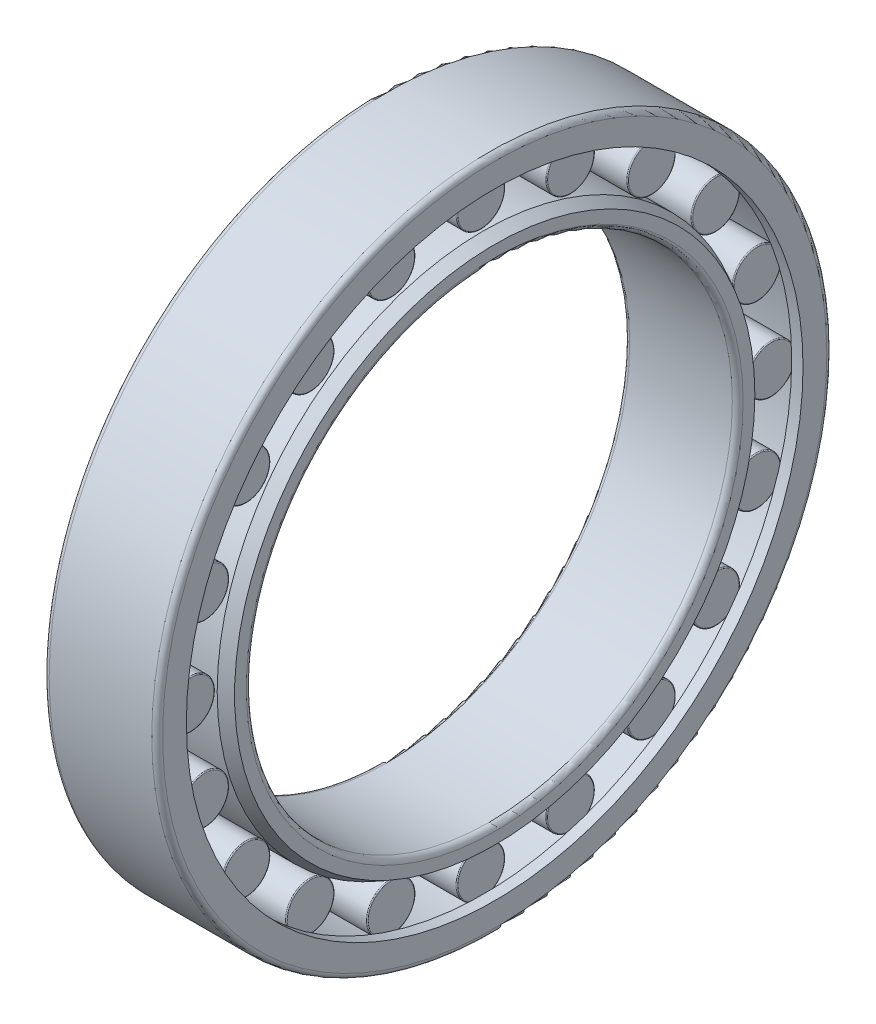
SolidWorks part; units mm, degrees
ref_plane "Plane1" through (0, 0, 0) normal (0, 0, 1) x (1, 0, 0)
ref_plane "Plane2" through (0, 0, 0) normal (0, 1, 0) x (1, 0, 0)
ref_plane "Plane3" through (0, 0, 0) normal (1, 0, 0) x (0, 0, -1)
sketch "Clipboard" plane through (0, 0, 0) normal (0, 0, 1) x (1, 0, 0)
  line L0 (-10, 0) -> (10, 0) construction
  line L1 (0, 0) -> (185.2698, -67.4327)
  line L2 (0, 0) -> (101.017, 36.7672)
  line L3 (0, 0) -> (218.798, -79.636)
  line L4 (0, 0) -> (-22.3471, -0.7804)
  dimension "Race_OD" = 232.84
  dimension "Race_ID" = 197.16
sketch "OutRacSke" plane through (0, 0, 0) normal (0, 0, 1) x (1, 0, 0)
  line L0 (-16.8, 114.1887) -> (-21, 114.1887)
  line L1 (-21, 114.1887) -> (-21, 123)
  line L2 (-19, 125) -> (19, 125)
  line L3 (21, 123) -> (21, 114.1888)
  line L4 (21, 114.1888) -> (16.8, 114.1888)
  line L5 (16.8, 114.1888) -> (16.8, 116.42)
  line L6 (16.8, 116.42) -> (-16.8, 116.42)
  line L7 (-16.8, 116.42) -> (-16.8, 114.1887)
  line L8 (-90, 0) -> (90, 0) construction
  arc A0 (-21, 123) -> (-19, 125) centre (-19, 123) cw
  arc A1 (19, 125) -> (21, 123) centre (19, 123) cw
  dimension "Race_OD" = 232.84
  dimension "radius" = 2
  dimension "halfWidth" = 21
  dimension "groove_dp" = 2.2313
  dimension "Cyl_Len" = 33.6
revolve "OuterRace" add sketch "OutRacSke" angle 360 about L8 reverse direction yes
sketch "RolDetSke" plane through (0, 0, 0) normal (0, 0, 1) x (1, 0, 0)
  line L0 (-15.96, 116.068) -> (-15.96, 107.5)
  line L1 (-15.96, 107.5) -> (15.96, 107.5)
  line L2 (15.96, 107.5) -> (15.96, 116.068)
  line L3 (15.603, 116.425) -> (-15.603, 116.425)
  line L4 (-33.6, 107.5) -> (33.6, 107.5) construction
  arc A0 (15.96, 116.068) -> (15.603, 116.425) centre (15.603, 116.068) ccw
  arc A1 (-15.603, 116.425) -> (-15.96, 116.068) centre (-15.603, 116.068) ccw
  dimension "radius" = 0.357
  dimension "Roller_diameter" = 17.85
  dimension "halfLength" = 15.96
revolve "RollerDetailed" add sketch "RolDetSke" angle 360 about L4 reverse direction yes
ref_axis "Axis1" through (-50, 0, 0) along (1, 0, 0)
sketch "RolSimSke" plane through (0, 101.6, 0) normal (0, 0, 1) x (1, 0, 0)
  line L0 (-15.96, 14.468) -> (-15.96, -2.668)
  line L1 (25.4, -101.6) -> (-25.4, -101.6) construction
  line L2 (15.96, -2.668) -> (15.96, 14.468)
  line L3 (15.603, 14.825) -> (-15.603, 14.825)
  line L5 (15.603, -3.025) -> (-15.603, -3.025)
  arc A0 (15.96, 14.468) -> (15.603, 14.825) centre (15.603, 14.468) ccw
  arc A1 (-15.603, 14.825) -> (-15.96, 14.468) centre (-15.603, 14.468) ccw
  arc A2 (15.96, -2.668) -> (15.603, -3.025) centre (15.603, -2.668) cw
  arc A3 (-15.603, -3.025) -> (-15.96, -2.668) centre (-15.603, -2.668) cw
  dimension "radius" = 0.357
  dimension "D1" = 98.575
  dimension "Roller_diameter" = 17.85
  dimension "halfLength" = 15.96
revolve "RollersSimplified" [suppressed] add sketch "RolSimSke" angle 360 about L1
sketch "InsRacSke" plane through (0, 0, 0) normal (0, 0, 1) x (1, 0, 0)
  line L0 (-16.8, 98.58) -> (-21, 96.3487)
  line L1 (-21, 96.3487) -> (-21, 92)
  line L2 (-19, 90) -> (19, 90)
  line L3 (21, 92) -> (21, 96.3487)
  line L4 (21, 96.3487) -> (16.8, 98.58)
  line L5 (16.8, 98.58) -> (-16.8, 98.58)
  line L6 (-90, 0) -> (90, 0) construction
  line L7 (0, 0) -> (0, 177.8) construction
  arc A0 (-21, 92) -> (-19, 90) centre (-19, 92) ccw
  arc A1 (19, 90) -> (21, 92) centre (19, 92) ccw
  dimension "radius" = 2
  dimension "Race_ID" = 197.16
  dimension "Width" = 42
  dimension "halfWidth" = 21
  dimension "groove_dp" = 2.2313
  dimension "Cyl_Len" = 33.6
revolve "InnerRace" add sketch "InsRacSke" angle 360 about L6 reverse direction yes
pattern_circular "RollersDetailed" count 20 every 18 about axis through (-50, 0, 0) along (1, 0, 0) of "RollerDetailed"
sketch "CagSpiSke" plane through (0, 0, 0) normal (0, 0, 1) x (1, 0, 0)
  line L0 (18.9, 105.2687) -> (18.9, 109.7313)
  line L1 (18.9, 109.7313) -> (-18.9, 109.7313)
  line L2 (-18.9, 109.7313) -> (-18.9, 105.2687)
  line L3 (-18.9, 105.2687) -> (18.9, 105.2687)
  line L4 (-90, 0) -> (90, 0) construction
revolve "CageSpine" [suppressed] add sketch "CagSpiSke" angle 360 about L4
equation "\"CLdia@Clipboard\" =  ( \"Race_OD@Clipboard\" + \"Race_ID@Clipboard\" )  / 4"
equation "\"Race_OD@OutRacSke\" = \"Race_OD@Clipboard\""
equation "\"halfCylLen@OutRacSke\" = \"Cyl_Len@OutRacSke\" / 2"
equation "\"RolCLRad@RolDetSke\" = \"CLdia@Clipboard\""
equation "\"Roller_diameter@RolDetSke\" =  ( \"Race_OD@Clipboard\" - \"Race_ID@Clipboard\" )  / 2 + .01"
equation "\"Roller_diameter@RolSimSke\" =  ( \"Race_OD@Clipboard\" - \"Race_ID@Clipboard\" )  / 2 + .01"
equation "\"radius@RolDetSke\" = \"Roller_diameter@RolDetSke\" / 50"
equation "\"Length@RolDetSke\" = \"Cyl_Len@OutRacSke\" * .95"
equation "\"halfLength@RolDetSke\" = \"Length@RolDetSke\" / 2"
equation "\"thickness@CagSpiSke\"  = \"Roller_diameter@RolDetSke\" * .25"
equation "\"Cag_IR@CagSpiSke\" =  \"RolCLRad@RolDetSke\" * 2 - \"thickness@CagSpiSke\""
equation "\"Rol_Length@RolSimSke\" = \"Cyl_Len@InsRacSke\" * .95"
equation "\"halfLength@RolSimSke\" = \"Rol_Length@RolSimSke\" / 2"
equation "\"radius@RolSimSke\" = \"radius@RolDetSke\""
equation "\"D1@RolSimSke\" = \"CLdia@Clipboard\" -  ( \"Roller_diameter@RolSimSke\" / 2 ) "
equation "\"Max_count@Clipboard\" = int( 3.14159265 / atn(( \"Roller_diameter@RolDetSke\" / 2) / sqr( \"RolCLRad@RolDetSke\"  *  \"RolCLRad@RolDetSke\" - ( \"Roller_diameter@RolDetSke\" / 2) *  ( \"Roller_diameter@RolDetSke\" / 2))))"
equation "\"Max_count@Clipboard\" = ((sgn( \"Max_count@Clipboard\" - \"Count@Clipboard\" )-1)*( \"Max_count@Clipboard\" - \"Count@Clipboard\" ))/-2+ \"Count@Clipboard\""
equation "\"Count@RollersDetailed\" = int( \"Show_count@Clipboard\" ) "
equation "\"Count@RollersDetailed\" = ((sgn( \"Count@RollersDetailed\" - \"Max_count@Clipboard\" )-1)*( \"Count@RollersDetailed\" - \"Max_count@Clipboard\" ))/-2+ \"Max_count@Clipboard\""
equation "\"Count@RollersDetailed\" = ((sgn( \"Count@RollersDetailed\" - \"Min_count@Clipboard\" )+1)*( \"Count@RollersDetailed\" - \"Min_count@Clipboard\"))/2 +\"Min_count@Clipboard\""
equation "\"Angle@RollersDetailed\" = 360.0 / \"Max_count@Clipboard\""
equation "\"radius@InsRacSke\" = \"radius@OutRacSke\""
equation "\"groove_dp@InsRacSke\" = \"groove_dp@OutRacSke\""
equation "\"Width@InsRacSke\" = \"Width@OutRacSke\""
equation "\"halfWidth@OutRacSke\" = \"Width@OutRacSke\" / 2"
equation "\"halfWidth@InsRacSke\" = \"Width@InsRacSke\" / 2"
equation "\"Race_ID@InsRacSke\" = \"Race_ID@Clipboard\""
equation "\"Cyl_Len@InsRacSke\" = \"Cyl_Len@OutRacSke\""
equation "\"Angle@CageSpine\" =  \"Angle@RollersDetailed\" * ( \"Count@RollersDetailed\" -1 + int( \"Count@RollersDetailed\" / \"Max_count@Clipboard\" ) )  + 0.001 -  int( \"Count@RollersDetailed\" / \"Max_count@Clipboard\" ) * 0.001"
equation "\"Angle@CageSpine\" =  \"Angle@CageSpine\" * int( \"Min_count@Clipboard\" / 2) + int(1 / \"Min_count@Clipboard\")  * 0.001"
equation "\"width@CagSpiSke\" =   ( \"Width@InsRacSke\" + \"Cyl_Len@InsRacSke\" )  / 2"
equation "\"halfwidth@CagSpiSke\" = \"width@CagSpiSke\" / 2"
